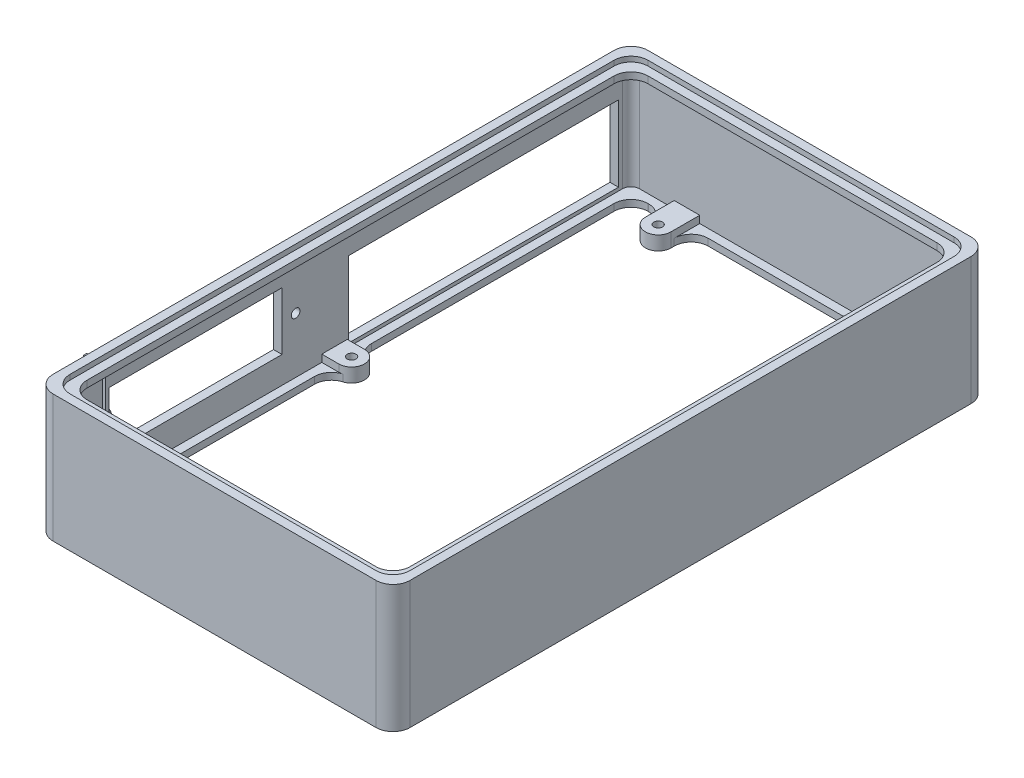
SolidWorks part; units mm, degrees
ref_plane "Front Plane" through (0, 0, 0) normal (0, 0, 1) x (1, 0, 0)
ref_plane "Top Plane" through (0, 0, 0) normal (0, 1, 0) x (1, 0, 0)
ref_plane "Right Plane" through (0, 0, 0) normal (1, 0, 0) x (0, 0, -1)
sketch "Sketch1" plane through (0, 0, 0) normal (0, 1, 0) x (1, 0, 0)
  line L0 (5, 5) -> (5, 345)
  line L1 (0, 0) -> (210, 0)
  line L2 (0, 0) -> (0, 350)
  line L3 (0, 350) -> (210, 350)
  line L4 (210, 0) -> (210, 350)
  line L5 (5, 345) -> (205, 345)
  line L6 (205, 5) -> (205, 345)
  line L7 (5, 5) -> (205, 5)
  dimension "D1" = 5
extrude "Boss-Extrude2" add sketch "Sketch1" along normal blind 75
ref_plane "Plane1" through (0, 3, 0) normal (0, -1, 0) x (-1, 0, 0)
sketch "Sketch3" plane through (0, 3, 0) normal (0, -1, 0) x (-1, 0, 0)
  line L0 (-5, 345) -> (-37.92, 345)
  line L1 (-205, 345) -> (-5, 345) construction
  line L2 (-5, 345) -> (-176, 345)
  line L3 (-37.92, 322.07) -> (-5, 322.07)
  line L4 (-5, 345) -> (-5, 5) construction
  line L5 (-170, 176.59) -> (-205, 176.59)
  line L6 (-15.06, 176.59) -> (-5, 176.59)
  line L7 (-5, 176.59) -> (-5, 164.59)
  line L8 (-5, 164.59) -> (-15.06, 164.59)
  line L9 (-205, 5) -> (-205, 345) construction
  line L10 (-170, 164.59) -> (-205, 164.59)
  line L11 (-37.92, 322.07) -> (-170, 322.07)
  line L12 (-170, 322.07) -> (-205, 322.07)
  line L13 (-43.92, 345) -> (-5, 345)
  line L14 (-5, 345) -> (-5, 322.07)
  line L15 (-15.06, 176.59) -> (-170, 176.59)
  line L16 (-15.06, 164.59) -> (-170, 164.59)
  line L17 (-5, 176.59) -> (-205, 176.59)
  line L18 (-5, 176.59) -> (-5, 164.59)
  line L19 (-5, 164.59) -> (-205, 164.59)
  line L20 (-205, 176.59) -> (-205, 164.59)
  line L21 (-205, 322.07) -> (-205, 345)
  line L22 (-205, 345) -> (-176, 345)
  circle A0 centre (-37.92, 328.07) radius 2.55
  circle A1 centre (-170, 328.07) radius 2.55
  circle A2 centre (-170, 170.59) radius 2.55
  circle A3 centre (-15.06, 170.59) radius 2.55
  circle A4 centre (-15.06, 170.59) radius 6
  circle A5 centre (-170, 170.59) radius 6
  circle A6 centre (-37.92, 328.07) radius 6
  circle A7 centre (-170, 328.07) radius 6
extrude "Boss-Extrude3" add sketch "Sketch3" against normal blind 6 contours A7 L11 A6 L3 L14 L0 L2 | A6 A0 | A7 A1 | A4 L8 L7 L6 | A4 A3 | A5 L16 A4 L15 | A5 L5 L20 L10 | A5 A2 region at (174.1226, 3, -332.1926) region at (42.0426, 3, -332.1926) region at (105.054, 3, -333.8185) region at (189.8266, 3, -170.59) region at (92.53, 3, -170.59) region at (165.8774, 3, -174.7126) region at (7.8415, 3, -170.59) region at (10.9374, 3, -174.7126)
sketch "Sketch4" plane through (5, 0, 0) normal (1, 0, 0) x (0, 0, -1)
  line L0 (345, 75) -> (337.62, 75)
  line L1 (345, 75) -> (5, 75) construction
  line L2 (337.62, 75) -> (337.62, 62)
  line L4 (337.62, 62) -> (178.87, 62)
  line L5 (337.62, 62) -> (337.62, 17.5)
  line L6 (337.62, 17.5) -> (178.87, 17.5)
  line L7 (178.87, 62) -> (178.87, 17.5)
extrude "Cut-Extrude1" cut sketch "Sketch4" against normal blind 66 contours L4 L7 L6 L5 region at (5, 39.75, -258.245)
sketch "Sketch5" plane through (0, 0, 0) normal (-1, 0, 0) x (0, 0, 1)
  line L0 (-178.87, 39.75) -> (-158.87, 39.75)
  line L1 (-178.87, 62) -> (-178.87, 17.5) construction
  line L2 (-158.87, 39.75) -> (-147.7, 39.75)
  line L3 (-147.7, 39.75) -> (-139.7, 39.75)
  line L4 (-139.7, 39.75) -> (-139.7, 35.75)
  line L5 (-139.7, 35.75) -> (-139.7, 43.75)
  line L6 (-139.7, 35.75) -> (-139.7, 22.75)
  line L7 (-139.7, 22.75) -> (-37.9, 22.75)
  line L8 (-37.9, 29.25) -> (-35.9, 29.25)
  line L9 (-139.7, 22.75) -> (-37.9, 22.75)
  line L10 (-139.7, 22.75) -> (-139.7, 35.75)
  line L11 (-139.7, 35.75) -> (-37.9, 35.75)
  line L12 (-37.9, 22.75) -> (-37.9, 35.75)
  line L13 (-139.7, 43.75) -> (-37.9, 43.75)
  line L14 (-139.7, 43.75) -> (-139.7, 56.75)
  line L15 (-139.7, 56.75) -> (-37.9, 56.75)
  line L16 (-37.9, 43.75) -> (-37.9, 56.75)
  line L17 (-35.9, 39.75) -> (-35.9, 14.75)
  line L18 (-35.9, 14.75) -> (-35.9, 67.75)
  line L20 (-35.9, 14.75) -> (-34.15, 14.75)
  line L21 (-35.9, 14.75) -> (-35.9, 67.75)
  line L22 (-35.9, 67.75) -> (-34.15, 67.75)
  line L23 (-34.15, 14.75) -> (-34.15, 67.75)
  circle A0 centre (-147.7, 39.75) radius 2.55
extrude "Cut-Extrude2" cut sketch "Sketch5" against normal blind 66 contours L3 A0 L2 | L2 A0 L3 | L7 L12 L11 L6 | L13 L16 L15 L14 | L20 L23 L22 L18 L17 region at (0, 40.8323, -147.7) region at (0, 50.25, -88.8) region at (0, 41.25, -35.025) region at (0, 29.25, -88.8) region at (0, 38.6677, -147.7)
ref_plane "Plane2" through (5, 43.75, -37.9) normal (-1, 0, 0) x (0, 0, 1)
sketch "Sketch7" plane through (0, 0, 0) normal (-1, 0, 0) x (0, 0, 1)
  line L1 (-35.9, 14.75) -> (-37.9, 14.75)
  line L2 (-35.9, 14.75) -> (-35.9, 67.75)
  line L3 (-35.9, 67.75) -> (-37.9, 67.75)
  line L4 (-37.9, 14.75) -> (-37.9, 67.75)
extrude "Boss-Extrude4" add sketch "Sketch7" along normal blind 8
sketch "Sketch8" plane through (0, 0, 0) normal (-1, 0, 0) x (0, 0, 1)
  line L1 (-139.7, 43.75) -> (-37.9, 43.75)
  line L2 (-139.7, 43.75) -> (-139.7, 35.75)
  line L3 (-139.7, 35.75) -> (-37.9, 35.75)
  line L4 (-37.9, 43.75) -> (-37.9, 35.75)
extrude "Cut-Extrude3" cut sketch "Sketch8" against normal blind 8
sketch "Sketch9" plane through (0, 0, -37.9) normal (0, 0, -1) x (-1, 0, 0)
  line L0 (-5, 52.4831) -> (0.5, 52.4831)
  line L1 (-5, 56.75) -> (-5, 22.75) construction
  line L2 (-5, 39.75) -> (0.5, 39.75)
  line L3 (0.5, 39.75) -> (0.5, 39.25)
  circle A0 centre (0.5, 39.25) radius 2.55
extrude "Cut-Extrude4" cut sketch "Sketch9" against normal blind 3
sketch "Sketch11" plane through (0, 0, -37.9) normal (0, 0, -1) x (-1, 0, 0)
  circle A0 centre (0.5, 39.25) radius 2.55
  circle A1 centre (0.5, 39.25) radius 4.5
extrude "Boss-Extrude5" add sketch "Sketch11" along normal blind 3
chamfer "Chamfer1" distance 3 angle 45 1 edges at (4, 39.25, -37.9)
sketch "Sketch12" plane through (0, 0, -35.9) normal (0, 0, 1) x (1, 0, 0)
  circle A0 centre (-0.5, 39.25) radius 4
extrude "Cut-Extrude5" cut sketch "Sketch12" along normal blind 46
ref_plane "Plane3" through (0, 72, 0) normal (0, 1, 0) x (1, 0, 0)
sketch "Sketch13" plane through (0, 72, 0) normal (0, 1, 0) x (1, 0, 0)
  line L0 (5, 345) -> (5, 5)
  line L1 (5, 92.9) -> (5, -17.1) construction
  line L2 (5, 345) -> (5, 5) construction
  line L3 (5, 5) -> (205, 5)
  line L4 (205, 5) -> (205, 345)
  line L5 (205, 345) -> (5, 345)
  line L6 (200, 340) -> (10, 340)
  line L7 (10, 340) -> (10, 10)
  line L8 (10, 10) -> (200, 10)
  line L9 (200, 10) -> (200, 340)
  dimension "D1" = 5
extrude "Boss-Extrude6" add sketch "Sketch13" against normal blind 4
sketch "Sketch14" plane through (0, 3, 0) normal (0, -1, 0) x (1, 0, 0)
  line L13 (205, -5) -> (205, -345)
  line L14 (205, -345) -> (5, -345)
  line L15 (5, -345) -> (5, -5)
  line L16 (5, 17.1) -> (5, -92.9) construction
  line L17 (5, -5) -> (205, -5) construction
  line L18 (5, -5) -> (205, -5)
  line L19 (10, -10) -> (200, -10)
  line L20 (200, -10) -> (200, -340)
  line L21 (200, -340) -> (10, -340)
  line L22 (10, -340) -> (10, -10)
  dimension "D1" = 5
extrude "Boss-Extrude7" add sketch "Sketch14" against normal blind 4
fillet "Fillet1" radius 10 7 edges at (5, 37.5, -5) (205, 37.5, -5) (210, 37.5, 0) (0, 17.6407, 0) (0, 37.5, -350) (205, 38.5, -345) (210, 37.5, -350)
fillet "Fillet2" radius 5 1 edges at (5, 38.5, -345)
fillet "Fillet3" radius 10 8 edges at (10, 70, -10) (5, 73.5, -5) (200, 70, -10) (205, 73.5, -5) (205, 73.5, -345) (200, 70, -340) (5, 73.5, -345) (10, 70, -340)
fillet "Fillet4" radius 10 4 edges at (205, 1.5, -5) (5, 1.5, -5) (5, 1.5, -345) (205, 1.5, -345)
sketch "Sketch16" plane through (0, 9, 0) normal (0, 1, 0) x (1, 0, 0)
  line L0 (165.5, 176.59) -> (19.56, 176.59)
  line L1 (205, 176.59) -> (5, 176.59) construction
  line L2 (19.56, 164.59) -> (165.5, 164.59)
  line L3 (5, 164.59) -> (205, 164.59) construction
  line L4 (30.42, 328.07) -> (30.42, 345)
  line L5 (45.42, 328.07) -> (45.42, 345)
  line L6 (162.5, 328.07) -> (162.5, 345)
  line L8 (195, 345) -> (10, 345)
  line L9 (5, 340) -> (5, 322.07)
  line L10 (5, 322.07) -> (205, 322.07)
  line L11 (205, 322.07) -> (205, 335)
  line L12 (195, 345) -> (10, 345)
  line L13 (5, 340) -> (5, 322.07)
  line L14 (5, 322.07) -> (205, 322.07)
  line L15 (205, 322.07) -> (205, 335)
  circle A0 centre (37.92, 328.07) radius 7.5
  circle A1 centre (170, 328.07) radius 7.5
  circle A2 centre (15.06, 170.59) radius 7.5
  circle A3 centre (170, 170.59) radius 7.5
  arc A6 (10, 345) -> (5, 340) centre (10, 340) ccw
  arc A7 (205, 335) -> (195, 345) centre (195, 335) ccw
  arc A8 (10, 345) -> (5, 340) centre (10, 340) ccw
  arc A9 (205, 335) -> (195, 345) centre (195, 335) ccw
  line M1 (205, 176.59) -> (5, 176.59)
  line M3 (5, 164.59) -> (205, 164.59)
  dimension "D1" = 0
extrude "Cut-Extrude8" cut sketch "Sketch16" against normal blind 10 contours A1 L6 L12 L5 A0 L14 | L12 A8 L13 L14 A0 L4 | A3 A2 M1 M3 region at (92.53, 9, -170.59) region at (17.9428, 9, -333.3465) region at (103.96, 9, -333.4947)
sketch "Sketch19" plane through (0, 9, 0) normal (0, 1, 0) x (1, 0, 0)
  line L0 (170, 320.57) -> (200, 320.57)
  line L1 (200, 20) -> (200, 330) construction
  line L2 (165.5, 164.59) -> (205, 164.59) construction
  line L3 (205, 164.59) -> (205, 176.59) construction
  line L4 (205, 176.59) -> (165.5, 176.59) construction
  line L5 (19.56, 176.59) -> (5, 176.59) construction
  line L6 (5, 176.59) -> (5, 164.59) construction
  line L7 (5, 164.59) -> (19.56, 164.59) construction
  line L8 (45.42, 345) -> (30.42, 345) construction
  line L9 (30.42, 345) -> (30.42, 328.07) construction
  line L10 (33.42, 322.07) -> (42.42, 322.07) construction
  line L11 (45.42, 328.07) -> (45.42, 345) construction
  line L12 (165.5, 322.07) -> (205, 322.07) construction
  line L13 (205, 322.07) -> (205, 335) construction
  line L14 (195, 345) -> (162.5, 345) construction
  line L15 (162.5, 345) -> (162.5, 328.07) construction
  line L16 (165.5, 164.59) -> (205, 164.59)
  line L17 (205, 164.59) -> (205, 176.59)
  line L18 (205, 176.59) -> (165.5, 176.59)
  line L19 (19.56, 176.59) -> (5, 176.59)
  line L20 (5, 176.59) -> (5, 164.59)
  line L21 (5, 164.59) -> (19.56, 164.59)
  line L22 (45.42, 345) -> (30.42, 345)
  line L23 (30.42, 345) -> (30.42, 328.07)
  line L24 (33.42, 322.07) -> (42.42, 322.07)
  line L25 (45.42, 328.07) -> (45.42, 345)
  line L26 (165.5, 322.07) -> (205, 322.07)
  line L27 (205, 322.07) -> (205, 335)
  line L28 (195, 345) -> (162.5, 345)
  line L29 (162.5, 345) -> (162.5, 328.07)
  line L30 (200, 320.57) -> (205, 320.57)
  line L31 (205, 320.57) -> (205, 322.07)
  line L32 (15.06, 178.09) -> (5, 178.09)
  line L33 (5, 178.09) -> (5, 176.59)
  line L34 (5, 176.59) -> (5, 164.59)
  line L35 (15.06, 163.09) -> (5, 163.09)
  line L36 (5, 163.09) -> (5, 164.59)
  line L37 (170, 178.09) -> (205, 178.09)
  line L38 (205, 178.09) -> (205, 163.09)
  line L39 (205, 163.09) -> (170, 163.09)
  circle A0 centre (37.92, 328.07) radius 7.5
  circle A1 centre (170, 328.07) radius 7.5
  arc A2 (165.5, 176.59) -> (165.5, 164.59) centre (170, 170.59) ccw construction
  arc A3 (19.56, 164.59) -> (19.56, 176.59) centre (15.06, 170.59) ccw construction
  arc A4 (30.42, 328.07) -> (33.42, 322.07) centre (37.92, 328.07) ccw construction
  arc A5 (42.42, 322.07) -> (45.42, 328.07) centre (37.92, 328.07) ccw construction
  arc A6 (162.5, 328.07) -> (165.5, 322.07) centre (170, 328.07) ccw construction
  arc A7 (205, 335) -> (195, 345) centre (195, 335) ccw construction
  arc A8 (165.5, 176.59) -> (165.5, 164.59) centre (170, 170.59) ccw
  arc A9 (19.56, 164.59) -> (19.56, 176.59) centre (15.06, 170.59) ccw
  arc A10 (30.42, 328.07) -> (33.42, 322.07) centre (37.92, 328.07) ccw
  arc A11 (42.42, 322.07) -> (45.42, 328.07) centre (37.92, 328.07) ccw
  arc A12 (162.5, 328.07) -> (165.5, 322.07) centre (170, 328.07) ccw
  arc A13 (205, 335) -> (195, 345) centre (195, 335) ccw
  circle A14 centre (15.06, 170.59) radius 7.5
  circle A15 centre (170, 170.59) radius 7.5
  line M12 (165.5, 322.07) -> (205, 322.07)
extrude "Boss-Extrude8" add sketch "Sketch19" against normal up to surface (6 mm away) contours L24 A0 | A1 M12 | A1 L0 L30 L31 L26 | A15 L18 L38 L37 | L18 A15 | A15 L39 L38 L16 | A15 L16 | A14 L32 L33 L19 | L19 A14 | A14 L21 L36 L35 | A14 L21 region at (189.0156, 9, -321.3061) region at (170, 9, -321.4645) region at (170, 9, -163.9845) region at (189.0156, 9, -163.8261) region at (170, 9, -177.1955) region at (189.0156, 9, -177.3539) region at (15.06, 9, -177.1955) region at (8.5759, 9, -177.4034) region at (8.5759, 9, -163.7766) region at (15.06, 9, -163.9845) region at (37.92, 9, -321.4645)
sketch "Sketch22" plane through (0, 3, 0) normal (0, -1, 0) x (1, 0, 0)
  line L0 (10, -322.07) -> (5, -322.07)
  line L1 (162.5, -345) -> (162.5, -340)
  line L2 (162.5, -345) -> (162.5, -328.07) construction
  line L3 (5, -340) -> (5, -15) construction
  line L4 (10, -20) -> (10, -330)
  line L5 (190, -10) -> (20, -10)
  line L6 (200, -330) -> (200, -20)
  line L7 (20, -340) -> (190, -340)
  line L8 (10, -20) -> (10, -330)
  line L9 (190, -10) -> (20, -10)
  line L10 (200, -330) -> (200, -20)
  line L11 (20, -340) -> (190, -340)
  line L12 (195, -345) -> (10, -345) construction
  line L13 (5, -340) -> (5, -15)
  line L14 (195, -345) -> (10, -345)
  arc A0 (5, -340) -> (10, -345) centre (10, -340) ccw construction
  arc A1 (5, -340) -> (10, -345) centre (10, -340) ccw
  arc A4 (20, -10) -> (10, -20) centre (20, -20) ccw
  arc A5 (200, -20) -> (190, -10) centre (190, -20) ccw
  arc A6 (190, -340) -> (200, -330) centre (190, -330) ccw
  arc A7 (10, -330) -> (20, -340) centre (20, -330) ccw
  arc A8 (20, -10) -> (10, -20) centre (20, -20) ccw
  arc A9 (200, -20) -> (190, -10) centre (190, -20) ccw
  arc A10 (190, -340) -> (200, -330) centre (190, -330) ccw
  arc A11 (10, -330) -> (20, -340) centre (20, -330) ccw
  line M11 (5, -322.07) -> (10, -322.07)
  line M25 (162.5, -328.07) -> (162.5, -345)
  dimension "D1" = 0
extrude "Boss-Extrude9" add sketch "Sketch22" against normal up to surface (4 mm away) contours A11 L8 L13 A1 L14 L11 M11 M25 region at (74.8453, 3, -341.2273) up to face at (7.5, 7, -250.08)
fillet "Fillet5" radius 10 6 edges at (200, 5, -163.09) (200, 5, -178.09) (10, 5, -163.09) (10, 5, -178.09) (30.42, 5, -340) (45.42, 5, -340)
sketch "Sketch23" plane through (5, 0, 0) normal (1, 0, 0) x (0, 0, -1)
  line L0 (328.07, 9) -> (328.07, 1.7)
  line L1 (337.62, 17.5) -> (337.62, 9)
  line L2 (337.62, 9) -> (178.87, 9)
  line L3 (178.87, 9) -> (178.87, 17.5)
  line L4 (178.87, 17.5) -> (337.62, 17.5)
  line L6 (330, 7) -> (345, 7)
  line L7 (330, 3) -> (330, 7)
  line L8 (328.07, 3) -> (330, 3)
  line L9 (328.07, 9) -> (328.07, 3)
  line L10 (345, 9) -> (328.07, 9)
  line L11 (345, 7) -> (345, 9)
  line L12 (330, 7) -> (345, 7)
  line L13 (330, 3) -> (330, 7)
  line L14 (328.07, 3) -> (330, 3)
  line L15 (328.07, 9) -> (328.07, 3)
  line L16 (345, 9) -> (328.07, 9)
  line L17 (345, 7) -> (345, 9)
  line M28 (337.62, 17.5) -> (178.87, 17.5)
  dimension "D1" = 0
extrude "Cut-Extrude9" cut sketch "Sketch23" against normal blind 10 contours L3 L2 L1 M28 region at (5, 13.25, -258.245)
sketch "Sketch24" plane through (5, 0, 0) normal (1, 0, 0) x (0, 0, -1)
  line L0 (337.62, 62) -> (337.62, 9) construction
  line L1 (178.87, 62) -> (337.62, 62)
  line L2 (178.87, 62) -> (178.87, 53.5)
  line L3 (178.87, 53.5) -> (337.62, 53.5)
  line L4 (337.62, 62) -> (337.62, 53.5)
extrude "Boss-Extrude10" add sketch "Sketch24" against normal up to surface (5 mm away) up to face at (0, 39.6389, -75.5222)
sketch "Sketch25" plane through (0, 9, 0) normal (0, 1, 0) x (1, 0, 0)
  line L0 (15.06, 178.09) -> (5, 178.09) construction
  line L1 (5, 178.09) -> (5, 163.09) construction
  line L2 (5, 163.09) -> (15.06, 163.09) construction
  line L3 (170, 163.09) -> (205, 163.09) construction
  line L4 (205, 163.09) -> (205, 178.09) construction
  line L5 (205, 178.09) -> (170, 178.09) construction
  line L6 (170, 320.57) -> (205, 320.57) construction
  line L7 (205, 320.57) -> (205, 335) construction
  line L8 (195, 345) -> (162.5, 345) construction
  line L9 (162.5, 345) -> (162.5, 328.07) construction
  line L10 (45.42, 345) -> (30.42, 345) construction
  line L11 (30.42, 345) -> (30.42, 328.07) construction
  line L12 (45.42, 328.07) -> (45.42, 345) construction
  line L13 (15.06, 178.09) -> (5, 178.09)
  line L14 (5, 178.09) -> (5, 163.09)
  line L15 (5, 163.09) -> (15.06, 163.09)
  line L16 (170, 163.09) -> (205, 163.09)
  line L17 (205, 163.09) -> (205, 178.09)
  line L18 (205, 178.09) -> (170, 178.09)
  line L19 (170, 320.57) -> (205, 320.57)
  line L20 (205, 320.57) -> (205, 335)
  line L21 (195, 345) -> (162.5, 345)
  line L22 (162.5, 345) -> (162.5, 328.07)
  line L23 (45.42, 345) -> (30.42, 345)
  line L24 (30.42, 345) -> (30.42, 328.07)
  line L25 (45.42, 328.07) -> (45.42, 345)
  arc A0 (15.06, 163.09) -> (15.06, 178.09) centre (15.06, 170.59) ccw construction
  arc A1 (170, 178.09) -> (170, 163.09) centre (170, 170.59) ccw construction
  arc A2 (162.5, 328.07) -> (170, 320.57) centre (170, 328.07) ccw construction
  arc A3 (205, 335) -> (195, 345) centre (195, 335) ccw construction
  arc A4 (30.42, 328.07) -> (45.42, 328.07) centre (37.92, 328.07) ccw construction
  arc A5 (15.06, 163.09) -> (15.06, 178.09) centre (15.06, 170.59) ccw
  arc A6 (170, 178.09) -> (170, 163.09) centre (170, 170.59) ccw
  arc A7 (162.5, 328.07) -> (170, 320.57) centre (170, 328.07) ccw
  arc A8 (205, 335) -> (195, 345) centre (195, 335) ccw
  arc A9 (30.42, 328.07) -> (45.42, 328.07) centre (37.92, 328.07) ccw
extrude "Boss-Extrude11" add sketch "Sketch25" along normal blind 2.23
sketch "Sketch27" plane through (0, 3, 0) normal (0, -1, 0) x (1, 0, 0)
  circle A0 centre (37.92, -328.07) radius 2.55 construction
  circle A1 centre (170, -328.07) radius 2.55 construction
  circle A2 centre (170, -170.59) radius 2.55 construction
  circle A3 centre (15.06, -170.59) radius 2.55 construction
  circle A4 centre (37.92, -328.07) radius 2.55
  circle A5 centre (170, -328.07) radius 2.55
  circle A6 centre (170, -170.59) radius 2.55
  circle A7 centre (15.06, -170.59) radius 2.55
extrude "Cut-Extrude10" cut sketch "Sketch27" against normal blind 49.23
sketch "Sketch28" plane through (0, 75, 0) normal (0, 1, 0) x (1, 0, 0)
  line L0 (105, 350) -> (105, 175)
  line L1 (200, 350) -> (10, 350) construction
  line L2 (105, 175) -> (105, 0)
  line L3 (10, 0) -> (200, 0) construction
  line L5 (105, 175) -> (-63.1229, 175)
  line L6 (105, 175) -> (105, -36.6445)
  line L7 (105, -36.6445) -> (-63.1229, -36.6445)
  line L8 (-63.1229, 175) -> (-63.1229, -36.6445)
  line L9 (105, 175) -> (-72.1194, 175)
  line L10 (105, 175) -> (105, 377.7587)
  line L11 (105, 377.7587) -> (-72.1194, 377.7587)
  line L12 (-72.1194, 175) -> (-72.1194, 377.7587)
  line L13 (105, 175) -> (253.443, 175)
  line L14 (105, 175) -> (105, -36.6445)
  line L15 (105, -36.6445) -> (253.443, -36.6445)
  line L16 (253.443, 175) -> (253.443, -36.6445)
  line L17 (105, 175) -> (253.443, 175)
  line L18 (105, 175) -> (105, 377.7587)
  line L19 (105, 377.7587) -> (253.443, 377.7587)
  line L20 (253.443, 175) -> (253.443, 377.7587)
fillet "Fillet6" radius 10 2 edges at (10, 5, -10) (200, 5, -10)
sketch "Sketch30" plane through (5, 0, 0) normal (1, 0, 0) x (0, 0, -1)
  line L0 (147.7, 39.75) -> (178.87, 39.75)
  line L1 (178.87, 53.5) -> (178.87, 9) construction
